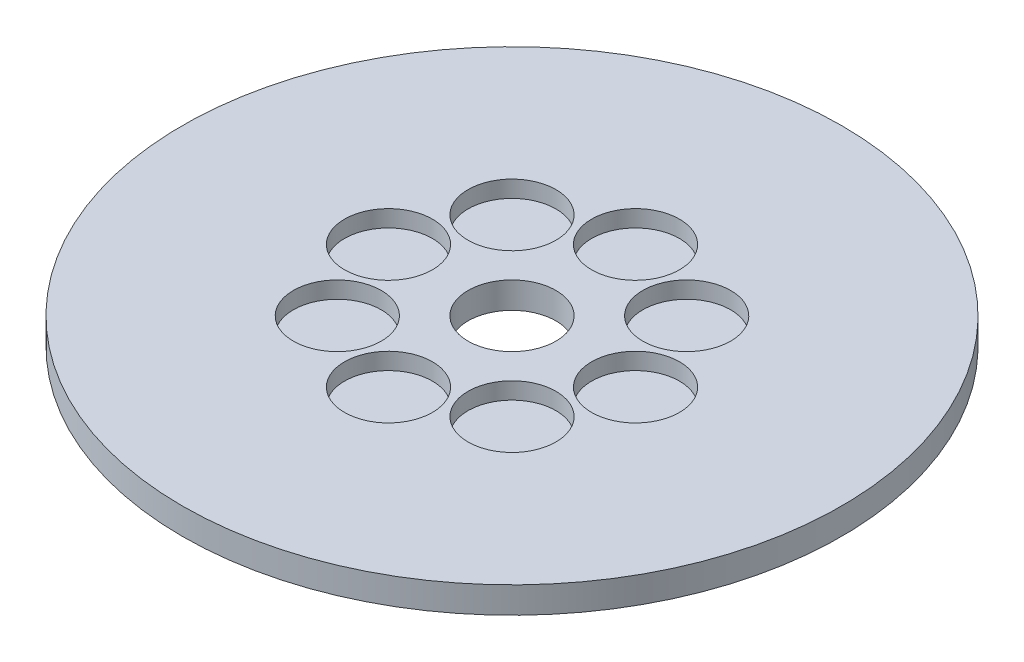
SolidWorks part; units mm, degrees
ref_plane "Front Plane" through (0, 0, 0) normal (0, 0, 1) x (1, 0, 0)
ref_plane "Top Plane" through (0, 0, 0) normal (0, 1, 0) x (1, 0, 0)
ref_plane "Right Plane" through (0, 0, 0) normal (1, 0, 0) x (0, 0, -1)
sketch "Sketch1" plane through (0, 0, 0) normal (0, 1, 0) x (1, 0, 0)
  circle A0 centre (0, 0) radius 75
  dimension "FLANGE_OD" = 150
extrude "Boss-Extrude1" add sketch "Sketch1" along normal blind 6
sketch "Sketch2" plane through (0, 0, 0) normal (0, 1, 0) x (1, 0, 0)
  circle A0 centre (0, 0) radius 10
  dimension "BORE_D" = 20
extrude "Cut-Extrude1" cut sketch "Sketch2" along normal through all
sketch "Sketch3" plane through (0, 6, 0) normal (0, 1, 0) x (1, 0, 0)
  circle A0 centre (0, 0) radius 28.1118 construction
  circle A1 centre (-28.1118, 0) radius 10
  dimension "BOLT_D" = 20
  dimension "BOLT_PCD" = 56.2237
extrude "Cut-Extrude2" cut sketch "Sketch3" against normal blind 3.8168
pattern_circular "CirPattern1" count 8 over 360 about axis through (0, 0, 0) along (0, 1, 0) of "Cut-Extrude2"
